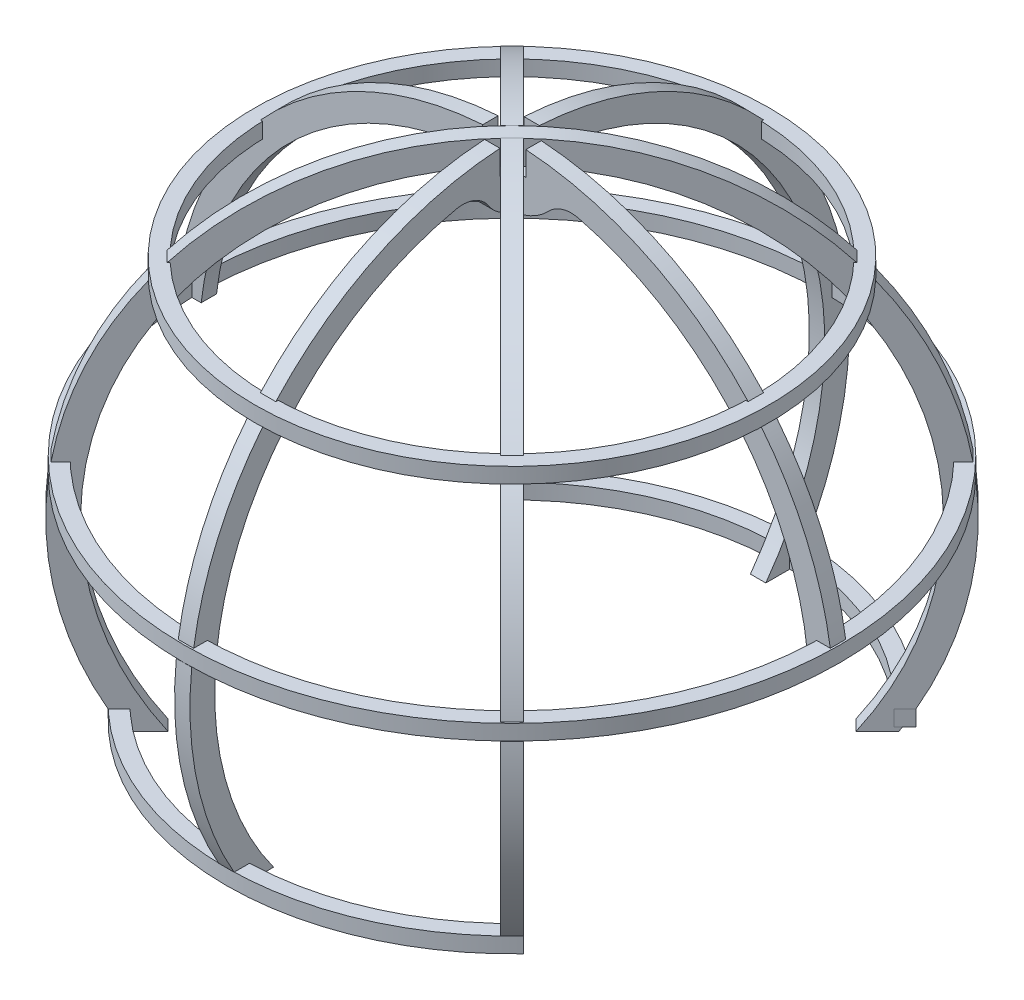
SolidWorks part; units mm, degrees
ref_plane "Front Plane" through (0, 0, 0) normal (0, 0, 1) x (1, 0, 0)
ref_plane "Top Plane" through (0, 0, 0) normal (0, 1, 0) x (1, 0, 0)
ref_plane "Right Plane" through (0, 0, 0) normal (1, 0, 0) x (0, 0, -1)
sketch "Sketch1" plane through (0, 0, 0) normal (0, 0, 1) x (1, 0, 0)
  line L0 (0, 0) -> (0, 6.985) construction
  line L1 (-49.53, -38.735) -> (49.53, -38.735) construction
  line L2 (-49.53, -38.735) -> (-49.53, 52.705) construction
  line L3 (-49.53, 52.705) -> (49.53, 52.705) construction
  line L4 (49.53, -38.735) -> (49.53, 52.705) construction
  line L5 (-49.53, -38.735) -> (49.53, 52.705) construction
  line L6 (-49.53, 52.705) -> (49.53, -38.735) construction
  line L7 (-49.53, 12.065) -> (49.53, 12.065) construction
  line L9 (-34.29, 12.065) -> (34.29, 12.065) construction
  line L10 (-34.29, 12.065) -> (-34.29, 52.705) construction
  line L11 (-34.29, 52.705) -> (34.29, 52.705) construction
  line L12 (34.29, 12.065) -> (34.29, 52.705) construction
  circle A0 centre (0, 0) radius 62.8778 construction
  circle A1 centre (0, 0) radius 67.9578 construction
  point P4 (0, 6.985)
  point P16 (0, 12.065)
  point P17 (0, 0)
  point P18 (0, 0)
  point P19 (0, 0)
  dimension "D2" = 5.08
  dimension "D3" = 91.44
  dimension "D4" = 50.8
  dimension "D5" = 68.58
  dimension "D6" = 99.06
sketch "Sketch2" plane through (0, 0, 0) normal (0, 0, 1) x (1, 0, 0)
  line L0 (-62.4886, 6.985) -> (62.4886, 6.985)
  line L1 (-49.53, -38.735) -> (49.53, -38.735) construction
  line L2 (-67.5979, 6.985) -> (-62.4886, 6.985)
  line L3 (62.4886, 6.985) -> (67.5979, 6.985)
  line L4 (0, 67.9578) -> (0, 6.985) construction
  line L5 (-49.53, -38.735) -> (49.53, 52.705) construction
  circle A0 centre (0, 0) radius 62.8778 construction
  circle A1 centre (0, 0) radius 67.9578 construction
  circle A2 centre (0, 0) radius 62.8778
  circle A3 centre (0, 0) radius 67.9578
  arc A4 (-12.6444, 66.7711) -> (12.6444, 66.7711) centre (0, 67.9578) ccw
  point P17 (0, 0)
  dimension "D2" = 12.7
  dimension "D1" = 45.72
extrude "Boss-Extrude1" add sketch "Sketch2" along normal mid plane 3.175 contours A4 A3 L2 A2 | L4 A3 A4 A2 | A3 L4 A2 A4 | A2 L4 A4 | L4 A2 A4 | A4 A2 L3 A3 region at (-65.0433, 7.8072, 0) region at (-6.0604, 65.0946, 0) region at (-4.3549, 59.5477, 0) region at (46.5257, 43.5093, 0) region at (4.3549, 59.5477, 0) region at (6.0604, 65.0946, 0)
ref_plane "Plane1" through (0, 0, 0) normal (0.7071, 0, -0.7071) x (0, 1, 0)
sketch "Sketch3" plane through (0, 0, 0) normal (0.7071, 0, -0.7071) x (0, 1, 0)
  line L0 (-38.735, -55.8604) -> (-38.735, 55.8604) construction
  line L1 (-38.735, -35.023) -> (-38.735, 35.023) construction
  line L2 (-37.1475, -56.9285) -> (-37.1475, 56.9285)
  line L3 (67.9564, -1.6489) -> (65.4271, -1.5875)
  line L4 (65.4271, -1.5875) -> (65.4271, 1.5875)
  line L5 (65.4271, 1.5875) -> (67.9578, 1.5875)
  line L7 (65.4271, 0) -> (62.8778, 0) construction
  line L8 (65.4271, 0) -> (67.9764, 0) construction
  circle A0 centre (0, 0) radius 67.9764
  circle A1 centre (0, 0) radius 62.8778
  ellipse E1 centre (0, 1.1225) end of major axis (67.9578, 1.1225) minor radius 48.0534 (6.985, -46.6764) -> (6.985, 48.9215) ccw construction
  ellipse E2 centre (0, 0) end of major axis (62.8778, 0) minor radius 44.4613 construction
  point P21 (-38.735, 0)
  dimension "D1" = 1.5875
  dimension "D2" = 3.175
extrude "Boss-Extrude2" add sketch "Sketch3" along normal mid plane 3.302 separate body contours A1 L2 A0 L3 L4 L5 region at (-38.0635, -35.4291, -38.0635)
ref_plane "Plane2" through (0, 0, 0) normal (-0.7071, 0, -0.7071) x (0, 1, 0)
sketch "Sketch4" plane through (0, 0, 0) normal (-0.7071, 0, -0.7071) x (0, 1, 0)
  line L0 (-38.735, -55.8379) -> (-38.735, 55.8379) construction
  line L1 (-38.735, -35.023) -> (-38.735, 35.023) construction
  line L2 (-37.9412, -56.3802) -> (-37.9412, 56.3802)
  line L3 (62.8578, -1.5875) -> (65.4178, -1.5875)
  line L4 (65.4178, -1.5875) -> (65.4178, 1.5875)
  line L5 (65.4178, 1.5875) -> (62.8578, 1.5875)
  line L7 (65.4178, 0) -> (67.9578, 0) construction
  line L8 (65.4178, 0) -> (62.8778, 0) construction
  circle A0 centre (0, 0) radius 67.9578
  circle A1 centre (0, 0) radius 62.8778
  ellipse E0 centre (0, 0) end of major axis (-67.9578, 0) minor radius 48.0534 construction
  ellipse E1 centre (0, 0) end of major axis (-62.8778, 0) minor radius 44.4613 construction
  point P20 (-38.735, 0)
  dimension "D1" = 1.5875
  dimension "D2" = 3.175
extrude "Boss-Extrude3" add sketch "Sketch4" along normal mid plane 3.175 separate body contours A1 L5 L4 L3 L2 A0 region at (-37.6608, -36.2182, 37.6608)
sketch "Sketch5" plane through (0, 0, 1.5875) normal (0, 0, 1) x (1, 0, 0)
  line L0 (4.445, 67.8123) -> (4.445, 62.8561)
  line L1 (4.445, 62.8561) -> (-4.445, 62.8561)
  line L2 (-4.445, 62.8561) -> (-4.445, 67.8123)
  line L3 (0, 67.9578) -> (0, 62.8561) construction
  arc A0 (67.5979, 6.985) -> (-67.5979, 6.985) centre (0, 0) ccw construction
  arc A1 (4.445, 67.8123) -> (-4.445, 67.8123) centre (0, 0) ccw
  ellipse E0 centre (-1.1674, 0) end of major axis (-1.1674, -62.8778) minor radius 44.4613 (34.7051, -37.1475) -> (-37.04, -37.1475) ccw construction
  point P9 (0, 60.5231)
  point P10 (0, 0)
  dimension "D1" = 8.89
extrude "Cut-Extrude1" cut sketch "Sketch5" against normal through all and the other way through all
ref_plane "Plane3" through (0, 67.9578, 0) normal (0, 1, 0) x (1, 0, 0)
ref_plane "Plane4" through (0, 42.5578, 0) normal (0, 1, 0) x (1, 0, 0)
sketch "Sketch6" plane through (0, 42.5578, 0) normal (0, 1, 0) x (1, 0, 0)
  line L2 (0, 0) -> (-36.3133, 38.6482) construction
  circle A0 centre (0, 0) radius 49.8565
  circle A1 centre (0, 0) radius 53.0315
  dimension "D1" = 3.175
extrude "Boss-Extrude4" add sketch "Sketch6" along normal blind 3.175 separate body
ref_plane "Plane5" through (0, 6.985, 0) normal (0, -1, 0) x (-1, 0, 0)
sketch "Sketch7" plane through (0, 6.985, 0) normal (0, -1, 0) x (-1, 0, 0)
  line L0 (67.5979, -1.5875) -> (67.5979, 1.5875) construction
  circle A0 centre (0, 0) radius 67.5979
  circle A1 centre (0, 0) radius 64.4229
  dimension "D1" = 3.175
extrude "Boss-Extrude5" add sketch "Sketch7" against normal blind 3.175 separate body
ref_plane "Plane6" through (0, -33.9725, 0) normal (0, -1, 0) x (-1, 0, 0)
sketch "Sketch8" plane through (0, -33.9725, 0) normal (0, -1, 0) x (-1, 0, 0)
  line L0 (40.4947, -38.2497) -> (42.7407, -40.4956)
  line L1 (0, 0) -> (40.4956, -42.7407) construction
  line L2 (-40.5383, -38.2035) -> (-42.7843, -40.4494)
  line L4 (-37.04, -34.7051) -> (-41.4219, -39.0871) construction
  line L5 (40.9894, -38.7443) -> (36.5773, -34.3322) construction
  line L6 (-40.4947, 38.2497) -> (-42.7407, 40.4956)
  line L7 (40.5383, 38.2035) -> (42.7843, 40.4494)
  line L8 (41.4219, 39.0871) -> (37.04, 34.7051) construction
  line L9 (-36.5773, 34.3322) -> (-40.9894, 38.7443) construction
  circle A0 centre (0, 0) radius 58.8783
  circle A1 centre (0, 0) radius 55.7033
  dimension "D1" = 3.175
extrude "Boss-Extrude6" add sketch "Sketch8" along normal blind 3.175 separate body contours A1 L7 A0 L6 | L1 A1 L2 A0 | A1 L1 A0 L0 region at (-40.5259, -33.9725, 40.4957) region at (-38.7808, -33.9725, 42.1784) region at (-0.0323, -33.9725, -56.5832)
sketch "Sketch9" plane through (1.1674, 0, -1.1674) normal (0.7071, 0, -0.7071) x (-0.7071, 0, -0.7071)
  line L3 (64.4017, 6.985) -> (64.4017, 10.16)
  line L4 (58.8552, -33.9725) -> (55.6788, -33.9725)
  line L5 (58.8552, -37.1475) -> (58.8552, -33.9725)
  line L6 (55.6788, -37.1475) -> (58.8552, -37.1475)
  line L7 (55.6788, -33.9725) -> (55.6788, -37.1475)
  line L8 (58.8552, -33.9725) -> (55.6788, -33.9725)
  line L9 (58.8552, -37.1475) -> (58.8552, -33.9725)
  line L10 (55.6788, -37.1475) -> (58.8552, -37.1475)
  line L11 (55.6788, -33.9725) -> (55.6788, -37.1475)
  line L12 (64.4017, 6.985) -> (67.6165, 6.985)
  line L13 (64.4017, 10.16) -> (67.2128, 10.16)
  line L14 (49.8292, 42.5578) -> (53.0058, 42.5578)
  line L15 (49.8292, 42.5578) -> (49.8292, 45.7328)
  line L16 (49.8292, 45.7328) -> (50.2921, 45.7328)
  line L17 (49.8565, 45.7328) -> (-49.8565, 45.7328) construction
  line L18 (-49.8565, 42.5578) -> (49.8565, 42.5578) construction
  line L19 (0, 0) -> (0, -35.7366) construction
  line L24 (-55.6788, -33.9725) -> (-55.6788, -37.1475)
  line L25 (-55.6788, -37.1475) -> (-58.8552, -37.1475)
  line L26 (-58.8552, -37.1475) -> (-58.8552, -33.9725)
  line L27 (-58.8552, -33.9725) -> (-55.6788, -33.9725)
  line L28 (-64.4017, 10.16) -> (-67.2128, 10.16)
  line L29 (-64.4017, 6.985) -> (-67.6165, 6.985)
  line L30 (-64.4017, 6.985) -> (-64.4017, 10.16)
  line L31 (-49.8292, 45.7328) -> (-50.2921, 45.7328)
  line L32 (-49.8292, 42.5578) -> (-49.8292, 45.7328)
  line L33 (-49.8292, 42.5578) -> (-53.0058, 42.5578)
  arc A0 (56.9285, -37.1475) -> (1.6489, 67.9564) centre (0, 0) ccw construction
  arc A1 (67.6165, 6.985) -> (67.2128, 10.16) centre (0, 0) ccw
  arc A2 (53.0058, 42.5578) -> (50.2921, 45.7328) centre (0, 0) ccw
  arc A3 (-67.6165, 6.985) -> (-67.2128, 10.16) centre (0, 0) cw
  arc A4 (-53.0058, 42.5578) -> (-50.2921, 45.7328) centre (0, 0) cw
  point P14 (0, 0)
  point P16 (0, 0)
  point P17 (0, 0)
  point P23 (0, 0)
  dimension "D1" = 0
extrude "Cut-Extrude2" cut sketch "Sketch9" against normal through all
sketch "Sketch10" plane through (1.1225, 0, 1.1225) normal (0.7071, 0, 0.7071) x (0.7071, 0, -0.7071)
  line L0 (67.5979, 6.985) -> (64.4033, 6.985)
  line L1 (64.4033, 6.985) -> (64.4033, 10.16)
  line L2 (64.4033, 10.16) -> (67.1941, 10.16)
  line L3 (52.982, 42.5578) -> (49.8313, 42.5578)
  line L4 (58.8569, -33.9725) -> (55.6807, -33.9725)
  line L5 (55.6807, -33.9725) -> (55.6807, -37.1475)
  line L6 (55.6807, -37.1475) -> (58.8569, -37.1475)
  line L7 (58.8569, -37.1475) -> (58.8569, -33.9725)
  line L8 (58.8569, -33.9725) -> (55.6807, -33.9725)
  line L9 (55.6807, -33.9725) -> (55.6807, -37.1475)
  line L10 (55.6807, -37.1475) -> (58.8569, -37.1475)
  line L11 (58.8569, -37.1475) -> (58.8569, -33.9725)
  line L12 (49.8313, 42.5578) -> (49.8313, 45.7328)
  line L13 (49.8313, 45.7328) -> (50.267, 45.7328)
  line L22 (0, 0) -> (0, -29.8904) construction
  line L23 (-58.8569, -37.1475) -> (-58.8569, -33.9725)
  line L24 (-55.6807, -37.1475) -> (-58.8569, -37.1475)
  line L25 (-55.6807, -33.9725) -> (-55.6807, -37.1475)
  line L26 (-58.8569, -33.9725) -> (-55.6807, -33.9725)
  line L27 (-64.4033, 10.16) -> (-67.1941, 10.16)
  line L28 (-64.4033, 6.985) -> (-64.4033, 10.16)
  line L29 (-67.5979, 6.985) -> (-64.4033, 6.985)
  line L30 (-49.8313, 45.7328) -> (-50.267, 45.7328)
  line L31 (-49.8313, 42.5578) -> (-49.8313, 45.7328)
  line L32 (-52.982, 42.5578) -> (-49.8313, 42.5578)
  arc A0 (56.3802, -37.9412) -> (-56.3802, -37.9412) centre (0, 0) ccw construction
  arc A1 (56.3802, -37.9412) -> (58.8569, -33.9725) centre (0, 0) ccw
  arc A2 (67.5979, 6.985) -> (67.1941, 10.16) centre (0, 0) ccw
  arc A3 (52.982, 42.5578) -> (50.267, 45.7328) centre (0, 0) ccw
  arc A4 (-56.3802, -37.9412) -> (-58.8569, -33.9725) centre (0, 0) cw
  arc A5 (-67.5979, 6.985) -> (-67.1941, 10.16) centre (0, 0) cw
  arc A6 (-52.982, 42.5578) -> (-50.267, 45.7328) centre (0, 0) cw
  arc M10 (56.3802, -37.9412) -> (-56.3802, -37.9412) centre (0, 0) ccw
  dimension "D1" = 0
extrude "Cut-Extrude3" cut sketch "Sketch10" against normal through all contours L26 L24 L25 M10 | L24 L23 M10 | L29 L28 L27 M10 | L32 L31 L30 M10 | L13 L12 L3 M10 | L2 L1 L0 M10 | L10 L11 M10 | L9 L10 L8 M10 region at (-39.0853, -35.3277, 41.3304) region at (-40.0405, -36.1001, 42.2856) region at (-45.4816, 8.5369, 47.7267) region at (-34.8767, 43.7511, 37.1217) region at (37.1217, 43.7511, -34.8767) region at (47.7267, 8.5369, -45.4816) region at (42.2856, -36.1001, -40.0405) region at (41.3304, -35.3277, -39.0853)
sketch "Sketch11" plane through (0, 0, -1.5875) normal (0, 0, -1) x (-1, 0, 0)
  line L0 (67.5979, 6.985) -> (64.4033, 6.985)
  line L1 (67.5979, 6.985) -> (62.4886, 6.985) construction
  line L2 (64.4033, 6.985) -> (64.4033, 10.16)
  line L3 (64.4033, 10.16) -> (67.1941, 10.16)
  line L8 (52.982, 42.5578) -> (49.8313, 42.5578)
  line L9 (49.8313, 42.5578) -> (49.8313, 45.7328)
  line L10 (49.8313, 45.7328) -> (50.267, 45.7328)
  line L15 (0, 55.2578) -> (0, 0) construction
  line L16 (-64.4033, 10.16) -> (-67.1941, 10.16)
  line L17 (-64.4033, 6.985) -> (-64.4033, 10.16)
  line L18 (-67.5979, 6.985) -> (-64.4033, 6.985)
  line L19 (-49.8313, 45.7328) -> (-50.267, 45.7328)
  line L20 (-49.8313, 42.5578) -> (-49.8313, 45.7328)
  line L21 (-52.982, 42.5578) -> (-49.8313, 42.5578)
  circle A0 centre (0, 0) radius 67.9578 construction
  arc A1 (67.5979, 6.985) -> (67.1941, 10.16) centre (0, 0) ccw
  arc A2 (52.982, 42.5578) -> (50.267, 45.7328) centre (0, 0) ccw
  arc A3 (-11.1518, 61.881) -> (11.1518, 61.881) centre (0, 67.9578) ccw construction
  arc A4 (-67.5979, 6.985) -> (-67.1941, 10.16) centre (0, 0) cw
  arc A5 (-52.982, 42.5578) -> (-50.267, 45.7328) centre (0, 0) cw
extrude "Cut-Extrude4" cut sketch "Sketch11" against normal through all
sketch "Sketch12" plane through (0, 0, 0) normal (1, 0, 0) x (0, 0, -1)
  line L0 (4.064, 65.2951) -> (-4.064, 65.2951) construction
  line L1 (1.5875, 55.2578) -> (-1.5875, 55.2578) construction
  line L2 (1.5875, 62.8561) -> (-1.5875, 62.8561) construction
  line L3 (0, 65.2951) -> (0, 62.8762) construction
  line L8 (0, 55.2578) -> (0, 62.8762) construction
  line L9 (55.8491, -38.735) -> (-55.8491, -38.735) construction
  line L10 (56.9174, -37.1475) -> (-56.9174, -37.1475)
  line L11 (4.064, 67.8455) -> (4.064, 62.7447)
  line L12 (-4.064, 67.8455) -> (-4.064, 62.7447)
  circle A0 centre (0, 0) radius 67.9671
  circle A1 centre (0, 0) radius 62.8762
  arc A2 (7.6044, 62.4147) -> (-7.6044, 62.4147) centre (0, 62.8762) cw
  point P9 (0, 62.8762)
  point P17 (0, -38.735)
  dimension "D1" = 1.5875
  dimension "D2" = 8.128
extrude "Boss-Extrude7" add sketch "Sketch12" along normal mid plane 3.175 separate body contours A1 L10 A0 L11 | A1 L12 A0 L10 | A2 A1 region at (0, -35.9184, -53.8234) region at (0, 30.0081, 59.611) region at (0, 59.5612, 0)
sketch "Sketch13" plane through (-1.5875, 0, 0) normal (-1, 0, 0) x (0, 0, 1)
  line L0 (67.6072, 6.985) -> (64.4033, 6.985)
  line L1 (64.4033, 6.985) -> (64.4033, 10.16)
  line L2 (64.4033, 10.16) -> (67.2034, 10.16)
  line L3 (52.9939, 42.5578) -> (49.8313, 42.5578)
  line L4 (49.8313, 42.5578) -> (49.8313, 45.7328)
  line L5 (49.8313, 45.7328) -> (50.2796, 45.7328)
  line L6 (49.8565, 45.7328) -> (-49.8565, 45.7328) construction
  line L13 (56.9174, -37.1475) -> (55.6807, -37.1475)
  line L14 (50.7295, -37.1475) -> (56.9174, -37.1475) construction
  line L15 (55.6807, -37.1475) -> (55.6807, -33.9725)
  line L16 (55.6807, -33.9725) -> (58.8676, -33.9725)
  line L21 (0, 0) -> (0, 55.2578) construction
  line L22 (-55.6807, -33.9725) -> (-58.8676, -33.9725)
  line L23 (-55.6807, -37.1475) -> (-55.6807, -33.9725)
  line L24 (-56.9174, -37.1475) -> (-55.6807, -37.1475)
  line L25 (-64.4033, 10.16) -> (-67.2034, 10.16)
  line L26 (-64.4033, 6.985) -> (-64.4033, 10.16)
  line L27 (-67.6072, 6.985) -> (-64.4033, 6.985)
  line L28 (-49.8313, 45.7328) -> (-50.2796, 45.7328)
  line L29 (-49.8313, 42.5578) -> (-49.8313, 45.7328)
  line L30 (-52.9939, 42.5578) -> (-49.8313, 42.5578)
  arc A0 (56.9174, -37.1475) -> (4.064, 67.8455) centre (0, 0) ccw construction
  arc A1 (56.9174, -37.1475) -> (58.8676, -33.9725) centre (0, 0) ccw
  arc A2 (67.6072, 6.985) -> (67.2034, 10.16) centre (0, 0) ccw
  arc A3 (52.9939, 42.5578) -> (50.2796, 45.7328) centre (0, 0) ccw
  arc A4 (-7.6044, 62.4147) -> (7.6044, 62.4147) centre (0, 62.8762) ccw construction
  arc A5 (-56.9174, -37.1475) -> (-58.8676, -33.9725) centre (0, 0) cw
  arc A6 (-67.6072, 6.985) -> (-67.2034, 10.16) centre (0, 0) cw
  arc A7 (-52.9939, 42.5578) -> (-50.2796, 45.7328) centre (0, 0) cw
extrude "Cut-Extrude5" cut sketch "Sketch13" against normal through all
sketch "Sketch14" plane through (0, 0, -1.5875) normal (0, 0, -1) x (-1, 0, 0)
  line L0 (-9.6326, 59.6811) -> (9.6326, 59.6811) construction
  line L1 (0, 59.6811) -> (0, 55.2578) construction
  line L2 (0, 59.6811) -> (0, 62.8561) construction
  line L3 (-1.5875, 62.8561) -> (-1.5875, 59.6811)
  line L4 (-1.5875, 59.6811) -> (1.5875, 59.6811)
  line L5 (1.5875, 59.6811) -> (1.5875, 62.8561)
  line L6 (4.445, 62.8561) -> (-4.445, 62.8561) construction
  line L7 (-1.5875, 62.8561) -> (1.5875, 62.8561)
  arc A0 (-11.1518, 61.881) -> (11.1518, 61.881) centre (0, 67.9578) ccw construction
  point P15 (0, 59.6811)
  dimension "D2" = 3.175
  dimension "D1" = 3.175
extrude "Cut-Extrude6" cut sketch "Sketch14" against normal through all
sketch "Sketch15" plane through (1.5875, 0, 0) normal (1, 0, 0) x (0, 0, -1)
  line L0 (-6.916, 59.6811) -> (6.916, 59.6811) construction
  line L1 (-1.5875, 59.6811) -> (-1.5875, 55.4251)
  line L2 (1.5875, 59.6811) -> (1.5875, 55.4251)
  line L3 (-1.5875, 59.6811) -> (1.5875, 59.6811)
  arc A0 (-7.6044, 62.4147) -> (7.6044, 62.4147) centre (0, 62.8762) ccw construction
  arc A3 (-1.5875, 55.4251) -> (1.5875, 55.4251) centre (0, 62.8762) ccw
extrude "Cut-Extrude7" cut sketch "Sketch15" against normal through all
fillet "Fillet1" radius 6.35 2 edges at (0, 62.4147, -7.6044) (0, 62.4147, 7.6044)
fillet "Fillet2" radius 6.35 2 edges at (-11.1518, 61.881, 0) (11.1518, 61.881, 0)
equation "\"thick\"= 0.125in"
equation "\"D1@Boss-Extrude1\"=\"thick\""
equation "\"D2@Sketch3\"=\"thick\""
equation "\"D2@Sketch4\"=\"thick\""
equation "\"D1@Boss-Extrude3\"=\"thick\""
equation "\"D1@Boss-Extrude4\"=\"thick\""
equation "\"D1@Boss-Extrude5\"=\"thick\""
equation "\"D1@Boss-Extrude6\"=\"thick\""
equation "\"D1@Boss-Extrude7\"=\"thick\""
equation "\"D2@Sketch14\"=\"thick\""
